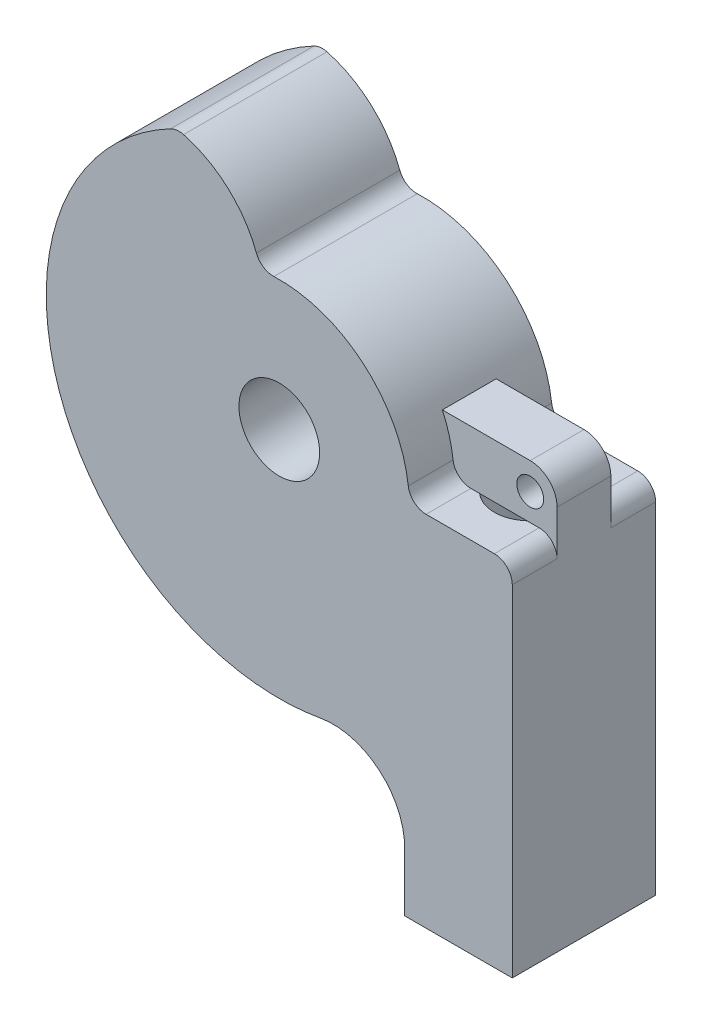
SolidWorks part; units mm, degrees
ref_plane "Front Plane" through (0, 0, 0) normal (0, 0, 1) x (1, 0, 0)
ref_plane "Top Plane" through (0, 0, 0) normal (0, 1, 0) x (1, 0, 0)
ref_plane "Right Plane" through (0, 0, 0) normal (1, 0, 0) x (0, 0, -1)
sketch "Sketch2" plane through (0, 0, 0) normal (0, 0, 1) x (1, 0, 0)
  line L0 (13, 0) -> (13, -20)
  line L1 (13, -20) -> (7, -20)
  line L2 (7, -20) -> (7, -10.9545)
  line L3 (10, 0) -> (10, -20) construction
  arc A0 (13, 0) -> (7, -10.9545) centre (0, 0) ccw
  circle A1 centre (0, 0) radius 10 construction
  dimension "Diameter" = 20
  dimension "Rod Holer Thickness" = 6
  dimension "Rod Holder Length" = 20
extrude "Boss-Extrude1" add sketch "Sketch2" along normal mid plane 8
hole_wizard "M4 Clearance Hole1" positions "Sketch3" profile "Sketch4" hole size "M4" standard "ANSI Metric" end condition up to next
sketch "Sketch3" plane through (0, 0, 4) normal (0, 0, 1) x (1, 0, 0)
  point P2 (0, 0)
sketch "Sketch4" plane through (0, 0, 4) normal (1, 0, 0) x (0, -1, 0)
  line L0 (0, 0) -> (0, 8)
  line L1 (0, 8) -> (2.25, 8)
  line L2 (2.25, 8) -> (2.25, 0)
  line L5 (2.25, 0) -> (0, 0)
  line L11 (0, -6.35) -> (0, 107.95) construction
  dimension "Thru Hole Dia." = 4.5
  dimension "Thru Hole Depth" = 8
sketch "Sketch5" plane through (0, -20, 0) normal (0, -1, 0) x (1, 0, 0)
  line L0 (13, 4) -> (7, -4) construction
  circle A0 centre (10, 0) radius 2
  dimension "Rod Hole Diameter" = 4
extrude "Cut-Extrude1" cut sketch "Sketch5" against normal blind 20
ref_axis "Axis1" through (10, 0, 0) along (0, -1, 0)
sketch "Sketch8" plane through (0, 0, -4) normal (0, 0, 1) x (1, 0, 0)
  line L0 (0, 0) -> (-21.8723, 0) construction
  line L1 (0, 0) -> (-6.8944, 5.7851) construction
  circle A0 centre (-6.8944, 5.7851) radius 3
  dimension "D2" = 6
  dimension "D1" = 40
  dimension "D3" = 9
extrude "Cut-Extrude3" cut sketch "Sketch8" along normal blind 5.5
sketch "Sketch9" plane through (0, 0, 4) normal (0, 0, 1) x (1, 0, 0)
  line L1 (13, 0) -> (7.25, 0)
  line L2 (13, 0) -> (13, 10.075) construction
  arc A0 (13, 0) -> (7, -10.9545) centre (0, 0) ccw construction
  arc A1 (7.25, 0) -> (-1.057, 7.1725) centre (0, 0) ccw
  circle A2 centre (0, 0) radius 2.25 construction
  arc A4 (-1.057, 7.1725) -> (-5.7272, 11.6705) centre (-6.8944, 5.7851) ccw
  circle A5 centre (-6.8944, 5.7851) radius 3 construction
  arc A6 (13, 0) -> (-5.7272, 11.6705) centre (0, 0) ccw
  dimension "D1" = 5
  dimension "D2" = 3
extrude "Cut-Extrude4" cut sketch "Sketch9" against normal through all
sketch "Sketch6" plane through (0, 0, 0) normal (0, 0, 1) x (1, 0, 0)
  line L4 (13, 1.5) -> (13, 0)
  line L6 (11.5, 3) -> (6.6002, 3)
  line L8 (7.25, 0) -> (13, 0) construction
  line L9 (7.25, 0) -> (13, 0)
  arc A2 (13, 1.5) -> (11.5, 3) centre (11.5, 1.5) ccw
  arc A3 (7.25, 0) -> (-1.057, 7.1725) centre (0, 0) ccw construction
  arc A4 (7.25, 0) -> (6.6002, 3) centre (0, 0) ccw
  dimension "Spring Attchment Diameter" = 1.5
extrude "Boss-Extrude2" add sketch "Sketch6" along normal mid plane 3
fillet "Fillet1" radius 1 6 edges at (-5.7272, 11.6705, 0) (7.25, 0, 2.75) (7.25, 0, -2.75) (-1.057, 7.1725, 0) (13, 0, -2.75) (13, 0, 2.75)
sketch "Sketch7" plane through (0, 0, 1.5) normal (0, 0, 1) x (1, 0, 0)
  circle A0 centre (11.5, 1.5) radius 0.75
  arc A1 (13, 1.5) -> (11.5, 3) centre (11.5, 1.5) ccw construction
  dimension "Spring Hole Diam" = 1.5
extrude "Cut-Extrude2" cut sketch "Sketch7" against normal through all both and the other way through all
fillet "Fillet2" radius 4 1 edges at (7, -10.9545, 0)
sketch "Sketch10" [suppressed] plane through (0, 0, -3) normal (0, 0, -1) x (-1, 0, 0)
  line L0 (-7, -10.9545) -> (-7, -20) construction
  line L1 (-7, -10.9545) -> (-7, -20)
  line L2 (-7, -20) -> (-1.5, -20)
  line L3 (-1.5, -20) -> (-1.5, -12.9132)
  arc A0 (-7, -10.9545) -> (6.0647, 11.4987) centre (0, 0) ccw construction
  arc A1 (-7, -10.9545) -> (-1.5, -12.9132) centre (0, 0) ccw
  circle A2 centre (-4.6, -16.5) radius 1.5
  dimension "D1" = 3
  dimension "D3" = 2
  dimension "D4" = 1.6
  dimension "D2" = 5.5
extrude "Boss-Extrude3" [suppressed] add sketch "Sketch10" against normal up to surface (6 mm away) up to face at (2.25, 0, 4)
fillet "Fillet3" [suppressed] radius 2
